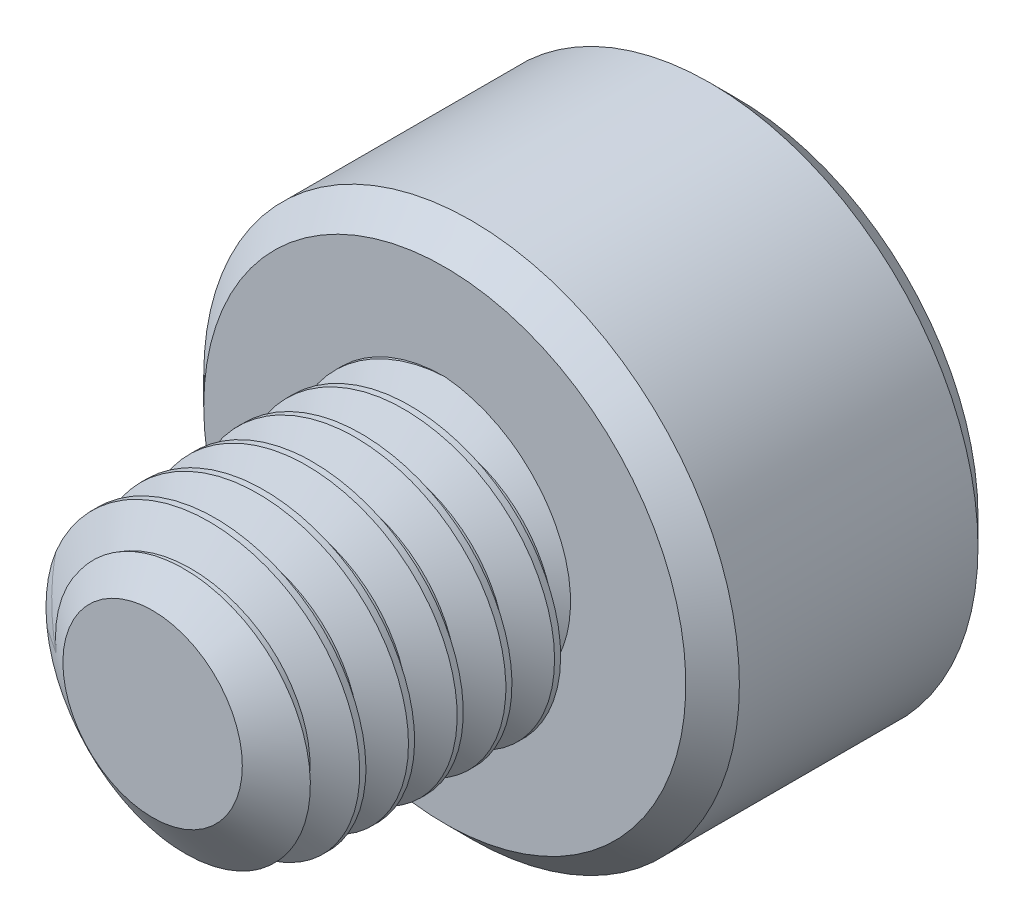
SolidWorks part; units mm, degrees
other "DetailItem1"
ref_plane "Front Plane" through (0, 0, 0) normal (0, 0, 1) x (1, 0, 0)
ref_plane "Top Plane" through (0, 0, 0) normal (0, 1, 0) x (1, 0, 0)
ref_plane "Right Plane" through (0, 0, 0) normal (1, 0, 0) x (0, 0, -1)
sketch "Sketch1" plane through (0, 0, 0) normal (0, 0, 1) x (1, 0, 0)
  circle A0 centre (0, 0) radius 1.5
  dimension "OD" = 3
extrude "Extrude1" add sketch "Sketch1" against normal blind 3
sketch "Sketch2" plane through (0, 0, 0) normal (0, 0, 1) x (1, 0, 0)
  circle A0 centre (0, 0) radius 1.5 construction
  circle A1 centre (0, 0) radius 1.5
curve "Helix/Spiral1" pitch 0.5 height 3.5 radius 1.5 centre (0, 0, 0) axis (0, 0, -1) start towards (0, 1, 0) parameters "pitch"=0.5
sketch "Sketch3" plane through (0, 0, 0) normal (1, 0, 0) x (0, 0, -1)
  line L0 (-0.4375, 1.5) -> (-0.25, 1.1752)
  line L1 (-0.25, 1.1752) -> (-0.1875, 1.1752)
  line L2 (-0.1875, 1.1752) -> (0, 1.5)
  line L3 (-0.4375, 1.5) -> (0, 1.5)
  line L4 (-0.2187, 1.5) -> (-0.2188, 1.1752) construction
  line L5 (-0.3438, 1.3376) -> (-0.0938, 1.3376) construction
  line L6 (0, 1.5) -> (0, -1.5) construction
  dimension "D1" = 0.0625
  dimension "D2" = 0.25
  dimension "D3" = 60
sweep "Cut-Sweep1" cut profiles "Sketch3" path "Helix/Spiral1"
sketch "Sketch4" plane through (0, 0, 0) normal (1, 0, 0) x (0, 0, -1)
  line L0 (0.4053, 1.5) -> (0, 0.9212)
  line L1 (0, 0.9212) -> (0, 1.5)
  line L2 (0.4053, 1.5) -> (0, 1.5)
  line L3 (-0.4375, 1.5) -> (0, 1.5) construction
  line L4 (0, 0) -> (7.0209, 0) construction
  dimension "D1" = 55
  dimension "D2" = 0.254
revolve "Cut-Revolve1" cut sketch "Sketch4" angle 360 about L4
sketch "Sketch6" plane through (0, 0, -3) normal (0, 0, -1) x (-1, 0, 0)
  circle A0 centre (0, 0) radius 2.75
  dimension "head dia" = 5.5
extrude "Extrude2" add sketch "Sketch6" along normal blind 3
sketch "Sketch7" plane through (0, 0, -6) normal (0, 0, -1) x (-1, 0, 0)
  line L1 (0, 1.4434) -> (-1.25, 0.7217)
  line L2 (-1.25, 0.7217) -> (-1.25, -0.7217)
  line L3 (-1.25, -0.7217) -> (0, -1.4434)
  line L4 (0, -1.4434) -> (1.25, -0.7217)
  line L5 (1.25, -0.7217) -> (1.25, 0.7217)
  line L6 (1.25, 0.7217) -> (0, 1.4434)
  circle A0 centre (0, 0) radius 1.25 construction
  dimension "hex dia" = 2.5
extrude "Cut-Extrude1" cut sketch "Sketch7" against normal blind 1.875
sketch "Sketch8" plane through (0, 0, -6) normal (0, 0, -1) x (-1, 0, 0)
  circle A0 centre (0, 0) radius 1.4434
extrude "Cut-Extrude2" cut sketch "Sketch8" against normal through all draft 45
chamfer "Chamfer1" distance 0.275 angle 45 2 edges at (-2.75, 0, -6) (-2.75, 0, -3)
sketch "Sketch10" plane through (0, 0, -3) normal (0, 0, 1) x (1, 0, 0)
  circle A1 centre (0, 0) radius 1.5
  circle A2 centre (0, 0) radius 1.5
  dimension "D1" = 0
ref_plane "Plane1" through (0, 0, 0) normal (0, 0, 1) x (1, 0, 0)
extrude "partial thread" [suppressed] add sketch "Sketch10" along normal up to surface (4 mm away) separate body up to plane "Plane1"
chamfer "Chamfer2" [suppressed] distance 0.06 angle 45
combine bodies "Combine1" [suppressed] operation type add bodies to combine 107 108
sketch "Sketch9" plane through (0, 0, 0) normal (1, 0, 0) x (0, 0, -1)
  line L0 (0, 1.5) -> (0, -1.5) construction
  line L1 (1.25, 1.5) -> (1.25, -1.5) construction
  dimension "D1" = 1.25
equation "\"D3@Helix/Spiral1\" = \"screw length@Extrude1\"+\"pitch@Helix/Spiral1\""
equation "\"D1@Sketch3\" = \"pitch@Helix/Spiral1\"*.125"
equation "\"D2@Sketch3\" = \"pitch@Helix/Spiral1\"*.5"
equation "\"D1@Cut-Extrude1\" = \"hex dia@Sketch7\"*.75"
equation "\"D1@Chamfer1\" = \"head dia@Sketch6\"*.05"
equation "\"D1@Sketch9\" = \"pitch@Helix/Spiral1\"*2.5"
equation "\"D1@Chamfer2\"=\"OD@Sketch1\"*.02"
